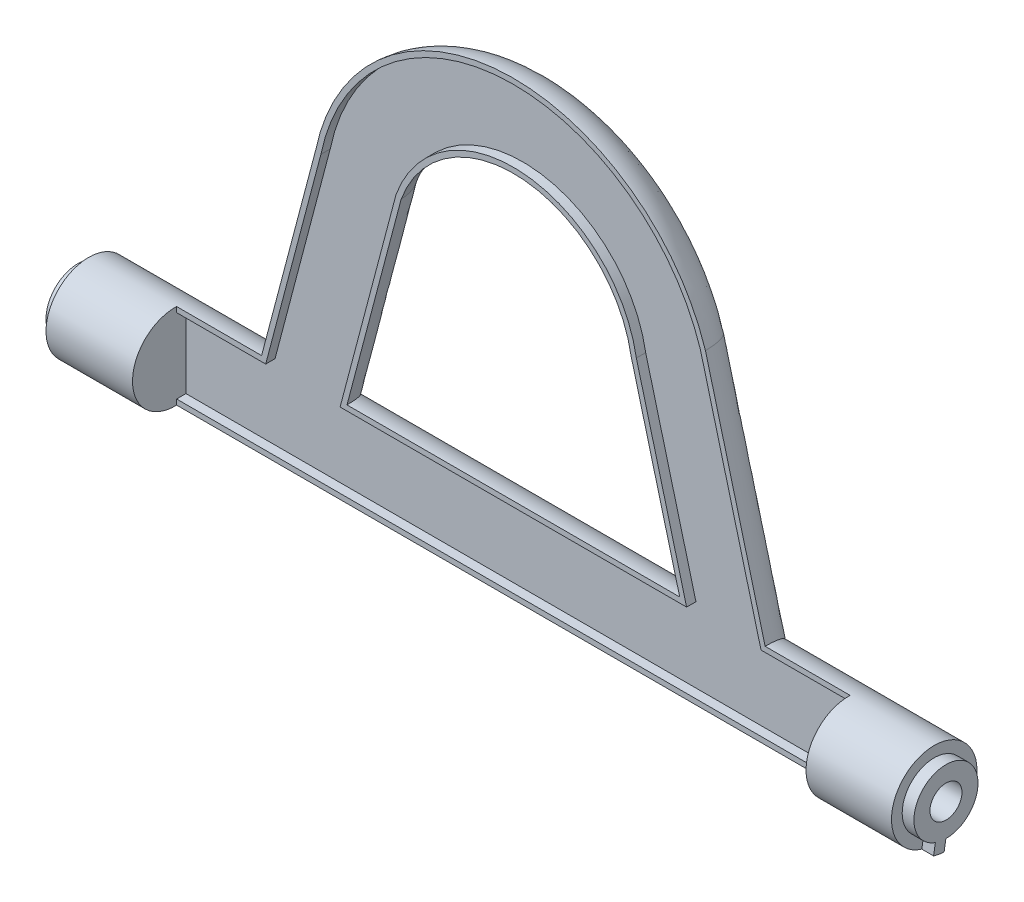
SolidWorks part; units mm, degrees
ref_plane "Piano frontale" through (0, 0, 0) normal (0, 0, 1) x (1, 0, 0)
ref_plane "Piano superiore" through (0, 0, 0) normal (0, 1, 0) x (1, 0, 0)
ref_plane "Piano destro" through (0, 0, 0) normal (1, 0, 0) x (0, 0, -1)
sketch "Schizzo1" plane through (0, 0, 0) normal (1, 0, 0) x (0, 0, -1)
  circle A0 centre (0, 0) radius 4
  dimension "D1" = 8
extrude "Estrusione-Estrusione1" add sketch "Schizzo1" along normal mid plane 81.25
sketch "Schizzo2" plane through (0, 0, 0) normal (0, 0, 1) x (1, 0, 0)
  line L0 (-39.2686, 0) -> (39.72, 0) construction
  line L1 (-20.625, 0) -> (-14.5039, 23.2063)
  line L2 (20.625, 0) -> (14.5039, 23.2063)
  line L3 (40.625, -4) -> (40.625, 4) construction
  line L4 (-40.625, 4) -> (-40.625, -4) construction
  arc A0 (-14.5039, 23.2063) -> (14.5039, 23.2063) centre (0, 19.3806) cw
  point P7 (0, 34.3806)
  dimension "D1" = 20
  dimension "D2" = 20
  dimension "D3" = 15
  dimension "D4" = 24
sketch "Schizzo3" plane through (0, 0, 0) normal (0, 1, 0) x (1, 0, 0)
  circle A0 centre (-20.625, 0) radius 4
  dimension "D1" = 8
sweep "Sweep1" add profiles "Schizzo3" path "Schizzo2"
sketch "Schizzo4" plane through (0, 0, 0) normal (1, 0, 0) x (0, 0, -1)
  line L6 (-4, 0) -> (4, 0) construction
  line L10 (-0.0099, -3) -> (-0.1742, -3.9962) construction
  line L17 (-0.0099, -3) -> (-0.1742, -3.9962)
  line L18 (-1.16, -3.8281) -> (-0.9954, -2.8301)
  line L19 (-0.9954, -2.8301) -> (-1.16, -3.8281) construction
  circle A15 centre (0, 0) radius 4 construction
  arc A16 (-0.1742, -3.9962) -> (-1.16, -3.8281) centre (0, 0) ccw
  arc A17 (-0.0099, -3) -> (-0.9954, -2.8301) centre (0, 0) ccw
  circle A18 centre (0, 0) radius 4 construction
  circle A19 centre (0, 0) radius 3 construction
  point P6 (0, 0)
  point P7 (0, 0)
  point P8 (0, 0)
  dimension "D3" = 1
  dimension "D1" = 6
  dimension "D2" = 1
  dimension "D4" = 0.9954
  dimension "D5" = 1.16
extrude "Taglio-Estrusione1" cut sketch "Schizzo4" against normal blind 1.1 from surface contours A17 L17 A16 L18 starting at face at (40.625, 0, -4)
sketch "Schizzo5" plane through (0, 0, 0) normal (1, 0, 0) x (0, 0, -1)
  line L6 (-1.16, -3.8281) -> (-0.9954, -2.8301)
  line L9 (-0.0099, -3) -> (-0.1742, -3.9962)
  line L10 (-1.16, -3.8281) -> (-0.9954, -2.8301)
  line L11 (-0.0099, -3) -> (-0.1742, -3.9962)
  arc A10 (-0.0099, -3) -> (-0.9954, -2.8301) centre (0, 0) ccw
  arc A11 (-0.1742, -3.9962) -> (-1.16, -3.8281) centre (0, 0) ccw
  arc A12 (-0.0099, -3) -> (-0.9954, -2.8301) centre (0, 0) ccw
  arc A13 (-0.1742, -3.9962) -> (-1.16, -3.8281) centre (0, 0) ccw
  dimension "D1" = 0
extrude "Taglio-Estrusione2" cut sketch "Schizzo5" along normal blind 1 from surface starting at face at (-40.625, 0, -4)
sketch "Schizzo6" plane through (0, 0, 0) normal (1, 0, 0) x (0, 0, -1)
  circle A0 centre (0, 0) radius 1.5
  dimension "D1" = 3
extrude "Taglio-Estrusione3" cut sketch "Schizzo6" along normal blind 6 from surface starting at face at (-40.625, -1.9535, 0.3331)
sketch "Schizzo7" plane through (0, 0, 0) normal (1, 0, 0) x (0, 0, -1)
  circle A0 centre (0, 0) radius 1.5 construction
  circle A1 centre (0, 0) radius 1.5
extrude "Taglio-Estrusione4" cut sketch "Schizzo7" against normal blind 6 from surface starting at face at (40.625, -1.9535, 0.3331)
sketch "Schizzo8" plane through (0, 0, 0) normal (0, 0, 1) x (1, 0, 0)
  line L0 (39.525, 4) -> (23.5699, 4) construction
  line L2 (-31.525, -3.5) -> (31.525, -3.5)
  line L3 (-31.525, -3.5) -> (-31.525, 3.5)
  line L5 (-31.525, 3.5) -> (-23.1847, 3.5)
  line L8 (31.525, -3.5) -> (31.525, 3.5)
  line L9 (-31.525, -3.5) -> (31.525, 3.5) construction
  line L10 (-31.525, 3.5) -> (31.525, -3.5) construction
  line L13 (39.525, -4) -> (39.525, 4) construction
  line L15 (23.5699, 4) -> (17.9836, 25.1792) construction
  line L18 (11.0243, 21.2334) -> (15.5699, 4) construction
  line L19 (-15.5699, 4) -> (-10.5039, 23.2063) construction
  line L42 (-18.5039, 23.2063) -> (-23.5699, 4) construction
  line L43 (23.5699, 4) -> (17.9836, 25.1792) construction
  line L44 (11.0243, 21.2334) -> (15.5699, 4) construction
  line L45 (-15.5699, 4) -> (-10.5039, 23.2063) construction
  line L46 (-18.5039, 23.2063) -> (-23.5699, 4) construction
  line L47 (23.0865, 3.8725) -> (17.5036, 25.0385)
  line L48 (-18.017, 23.0919) -> (-23.0865, 3.8725)
  line L49 (-16.0534, 4.1275) -> (-10.9816, 23.3557)
  line L50 (11.5136, 21.3391) -> (16.0534, 4.1275)
  line L51 (-23.0865, 3.8725) -> (-23.1847, 3.5)
  line L52 (-16.0534, 4.1275) -> (-16.2189, 3.5)
  line L53 (16.0534, 4.1275) -> (16.2189, 3.5)
  line L54 (23.0865, 3.8725) -> (23.1847, 3.5)
  line L55 (-16.2189, 3.5) -> (16.2189, 3.5)
  line L56 (23.1847, 3.5) -> (31.525, 3.5)
  arc A1 (11.0243, 21.2334) -> (-10.5039, 23.2063) centre (0, 19.3806) ccw construction
  arc A3 (17.9836, 25.1792) -> (-18.5039, 23.2063) centre (0, 19.3806) ccw construction
  arc A6 (11.0243, 21.2334) -> (-10.5039, 23.2063) centre (0, 19.3806) ccw construction
  arc A7 (17.9836, 25.1792) -> (-18.5039, 23.2063) centre (0, 19.3806) ccw construction
  arc A8 (17.5036, 25.0385) -> (-18.017, 23.0919) centre (0, 19.3806) ccw
  arc A9 (11.5136, 21.3391) -> (-10.9816, 23.3557) centre (0, 19.3806) ccw
  point P0 (0, 0)
  dimension "D1" = 0.5
  dimension "D2" = 8
  dimension "D3" = 0.5
  dimension "D4" = 0.5
extrude "Taglio-Estrusione5" cut sketch "Schizzo8" against normal blind 6 from offset 5
sketch "Schizzo9" plane through (0, 0, 0) normal (0, 1, 0) x (1, 0, 0)
  line L1 (-31.525, -4) -> (31.525, -4)
  line L2 (-31.525, -4) -> (-31.525, 0.127)
  line L3 (-31.525, 0.127) -> (31.525, 0.127)
  line L4 (31.525, -4) -> (31.525, 0.127)
  line L5 (31.525, 1) -> (31.525, -1.9365) construction
  line L6 (-31.525, -1.9365) -> (-23.2018, -1.9365) construction
  line L7 (-31.525, 1) -> (-31.525, -1.9365) construction
  point P5 (0, 0)
  point P6 (-31.525, -1.9365)
extrude "Taglio-Estrusione7" cut sketch "Schizzo9" against normal through all both and the other way through all
